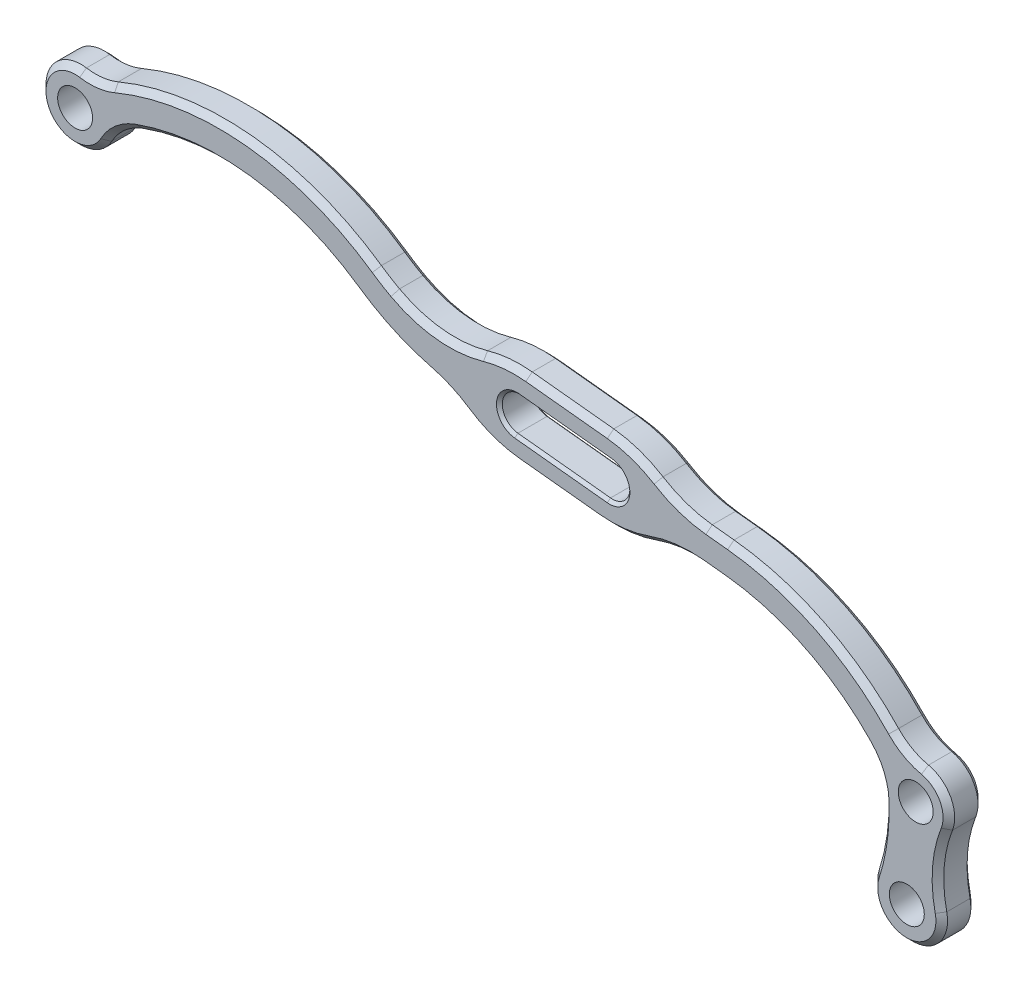
SolidWorks part; units mm, degrees
ref_plane "Спереди" through (0, 0, 0) normal (0, 0, 1) x (1, 0, 0)
ref_plane "Сверху" through (0, 0, 0) normal (0, 1, 0) x (1, 0, 0)
ref_plane "Справа" through (0, 0, 0) normal (1, 0, 0) x (0, 0, -1)
other "Configuration Table"
sketch "Sketch1" plane through (0, 0, 5) normal (0, 0, 1) x (1, 0, 0)
  line L0 (72.4787, 6.0336) -> (94.9418, 3.6726)
  line L1 (80.4883, 8.2083) -> (89.9363, 7.2152) construction
  line L2 (36.385, 6.5) -> (39, 6.5)
  line L3 (35.2523, 11.1565) -> (36.385, 6.5)
  line L4 (80.4883, 8.2083) -> (89.9363, 7.2152) construction
  arc A0 (40.881, 10.4938) -> (63.9587, 9.1988) centre (51.3653, -8.9473) cw
  circle A1 centre (111.1997, -6.0169) radius 2.85
  arc A2 (39, 6.5) -> (37.6854, 12.1966) centre (39, 9.5) ccw
  arc A3 (35.2523, 11.1565) -> (37.6854, 12.1966) centre (26, 36.1667) ccw
  arc A4 (39, 6.5) -> (37.6854, 12.1966) centre (39, 9.5) ccw construction
  circle A6 centre (111.1997, -6.0169) radius 2.85
  circle A7 centre (110.4359, -14.0152) radius 1.5 construction
  circle A8 centre (110.4359, -14.0152) radius 3
  circle A9 centre (110.4359, -14.0152) radius 1.5
  circle A10 centre (111.1997, -6.0169) radius 1.5
  arc A11 (108.36, -6.2592) -> (107.5809, -13.0939) centre (90.9923, -7.7411) cw
  arc A12 (113.8545, -7.0535) -> (113.3652, -13.3677) centre (124.0032, -11.016) ccw
  circle A13 centre (39, 9.5) radius 3
  circle A14 centre (39, 9.5) radius 1.5
  arc A15 (63.9587, 9.1988) -> (72.4787, 6.0336) centre (74.3914, 24.2316) ccw
  arc A17 (94.9418, 3.6726) -> (109.7835, -4.7641) centre (92.7146, -17.5185) cw
  circle A18 centre (84.8987, 4.7282) radius 1.5 construction
  circle A19 centre (84.8987, 4.7282) radius 1.5
  arc A22 (64.2892, 10.447) -> (76.3424, 5.2756) centre (78.6577, 27.304) ccw construction
  circle M8 centre (39, 9.5) radius 1.5
  arc M10 (39, 6.5) -> (37.6854, 12.1966) centre (39, 9.5) ccw
  dimension "D3" = 6
  dimension "D4" = 3
  dimension "D5" = 6
  dimension "D6" = 3
  dimension "D1" = 0
  dimension "D2" = 0
extrude "Boss-Extrude1" add sketch "Sketch1" along normal blind 3 contours A13 M10 M8 | A6 A10 | A12 A6 A11 A8 | A8 A9 region at (112.2601, -3.4586, 5) region at (41.8306, 10.1969, 5) region at (110.6816, -9.9328, 5) region at (110.5737, -11.1033, 5)
sketch "Sketch3" plane through (0, 0, 5) normal (0, 0, 1) x (1, 0, 0)
  line L0 (72.4787, 6.0336) -> (94.9418, 3.6726) construction
  line L1 (72.4787, 6.0336) -> (94.9418, 3.6726)
  arc A0 (109.7835, -4.7641) -> (94.9418, 3.6726) centre (92.7146, -17.5185) ccw construction
  arc A1 (63.9587, 9.1988) -> (72.4787, 6.0336) centre (74.3914, 24.2316) ccw construction
  arc A2 (63.9587, 9.1988) -> (40.881, 10.4938) centre (51.3653, -8.9473) ccw construction
  arc A3 (109.7835, -4.7641) -> (94.9418, 3.6726) centre (92.7146, -17.5185) ccw
  arc A4 (63.9587, 9.1988) -> (72.4787, 6.0336) centre (74.3914, 24.2316) ccw
  arc A5 (63.9587, 9.1988) -> (40.881, 10.4938) centre (51.3653, -8.9473) ccw
extrude "Extrude-Thin1" add sketch "Sketch3" along normal blind 3 thin thin type mid plane wall 3
sketch "Sketch4" plane through (0, 0, 8) normal (0, 0, 1) x (1, 0, 0)
  line L0 (71.8385, 9.6201) -> (90.7344, 7.6341)
  line L1 (71.8385, 9.6201) -> (71.1068, 2.6585)
  line L2 (90.7344, 7.6341) -> (90.0027, 0.6724)
  line L3 (71.1068, 2.6585) -> (90.0027, 0.6724)
  line L4 (95.0986, 5.1644) -> (72.6355, 7.5254) construction
  line L5 (95.0986, 5.1644) -> (72.6355, 7.5254) construction
  line L7 (94.785, 2.1808) -> (72.3219, 4.5418) construction
  line L8 (76.9425, 5.5644) -> (84.8987, 4.7282) construction
  line L9 (77.0993, 7.0562) -> (85.0555, 6.22)
  line L10 (76.7857, 4.0726) -> (84.7419, 3.2364)
  circle A36 centre (84.8987, 4.7282) radius 1.5
  circle A37 centre (84.8987, 4.7282) radius 1.5 construction
  arc A38 (77.0993, 7.0562) -> (76.7857, 4.0726) centre (76.9425, 5.5644) ccw
  arc A39 (84.7419, 3.2364) -> (85.0555, 6.22) centre (84.8987, 4.7282) ccw
  point P5 (80.9206, 5.1463)
  dimension "D1" = 2
  dimension "D4" = 1.5
  dimension "D7" = 4
  dimension "D2" = 2
  dimension "D5" = 8
  dimension "D6" = 4
  dimension "D3" = 0
extrude "Boss-Extrude2" add sketch "Sketch4" against normal up to surface (3 mm away) up to face at (86.0676, 0.9668, 5)
fillet "Fillet1" radius 10 4 edges at (90.0027, 0.6724, 6.5) (90.7344, 7.6341, 6.5) (71.1068, 2.6585, 6.5) (71.8385, 9.6201, 6.5)
fillet "Fillet2" radius 10 4 edges at (90.2118, 2.6615, 6.5) (71.3186, 4.6732, 6.5) (71.6326, 7.6614, 6.5) (90.5254, 5.6451, 6.5)
fillet "Fillet3" radius 5 4 edges at (108.4097, -5.435, 6.5) (110.5094, -3.2518, 6.5) (41.9978, 9.3861, 6.5) (40.5973, 12.0394, 6.5)
extrude "Cut-Extrude2" cut sketch "Sketch4<2>" against normal blind 3 contours A38 L10 A39 L9
sketch "Sketch4<2>" plane through (0, 0, 8) normal (0, 0, 1) x (1, 0, 0) same geometry as "Sketch4"
chamfer "Chamfer1" distance 0.25 angle 45 8 edges at (86.3905, 4.5714, 5) (81.0774, 6.6381, 5) (80.7638, 3.6545, 5) (75.4508, 5.7212, 5) (86.3905, 4.5714, 8) (81.0774, 6.6381, 8) (80.7638, 3.6545, 8) (75.4508, 5.7212, 8)
fillet "Fillet4" radius 0.5 54 edges at (75.8318, 9.0125, 5) (81.2661, 8.6293, 5) (86.9646, 7.7757, 5) (91.0309, 5.8465, 5) (94.1635, 5.2627, 5) (102.7851, 2.9457, 5) (110.4079, -2.7042, 5) (113.7101, -4.6677, 5) (113.1409, -10.1742, 5) (110.2941, -17.0118, 5) (108.2583, -10.1322, 5) (108.0198, -5.3349, 5) (101.4396, 0.2642, 5) (93.8499, 2.2791, 5) (90.6644, 2.3593, 5) (86.2859, 1.3177, 5) (80.5718, 1.6637, 5) (74.7466, 2.5711, 5) (66.1672, 6.2223, 5) (54.0154, 11.4693, 5) (42.7734, 9.4873, 5) (36.3099, 8.172, 5) (40.8653, 12.4347, 5) (53.8144, 14.5131, 5) (65.5775, 9.9313, 8) (75.8318, 9.0125, 8) (81.2661, 8.6293, 8) (86.9646, 7.7757, 8) (91.0309, 5.8465, 8) (94.1635, 5.2627, 8) (102.7851, 2.9457, 8) (110.4079, -2.7042, 8) (113.7101, -4.6677, 8) (113.1409, -10.1742, 8) (110.2941, -17.0118, 8) (108.2583, -10.1322, 8) (108.0198, -5.3349, 8) (101.4396, 0.2642, 8) (93.8499, 2.2791, 8) (90.6644, 2.3593, 8) (86.2859, 1.3177, 8) (80.5718, 1.6637, 8) (74.7466, 2.5711, 8) (66.1672, 6.2223, 8) (54.0154, 11.4693, 8) (42.7734, 9.4873, 8) (36.3099, 8.172, 8) (40.8653, 12.4347, 8) (65.5775, 9.9313, 5) (53.8144, 14.5131, 8) (70.0687, 8.3171, 5) (71.0975, 4.4899, 5) (70.0687, 8.3171, 8) (71.0975, 4.4899, 8) profile chamfer
